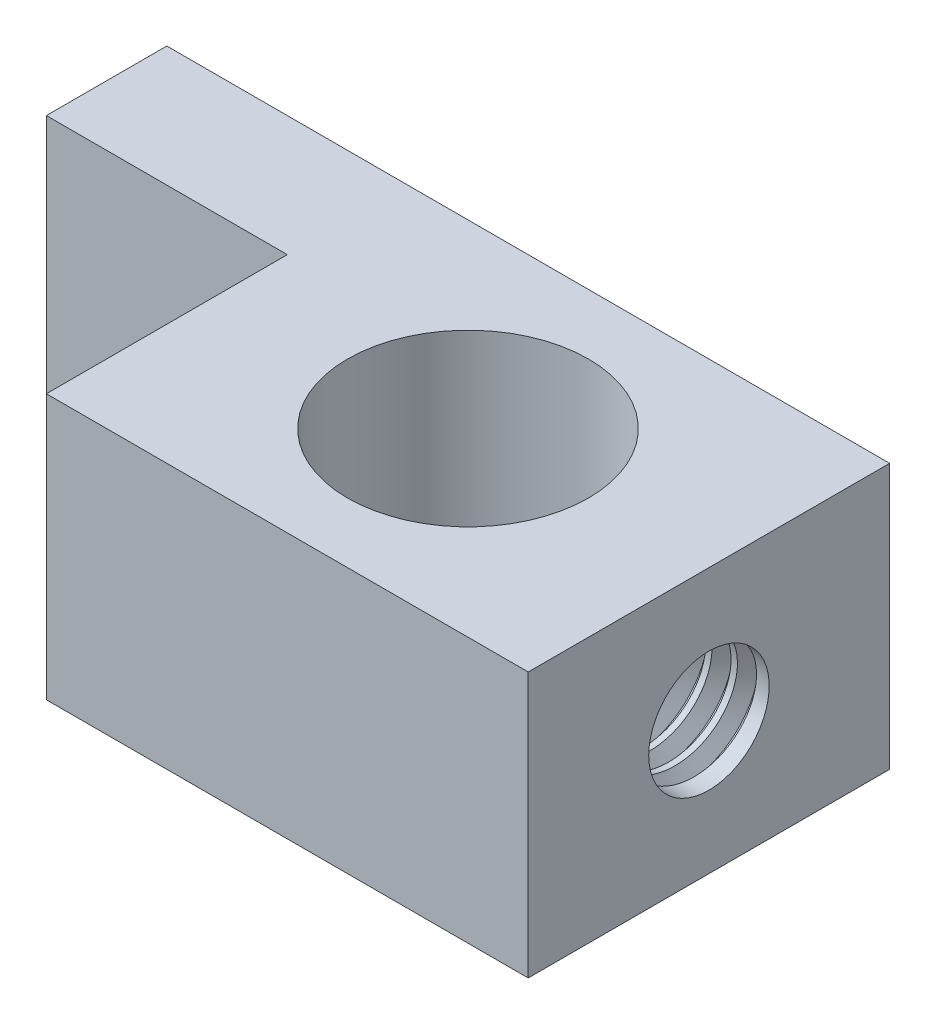
SolidWorks part; units mm, degrees
ref_plane "Front Plane" through (0, 0, 0) normal (0, 0, 1) x (1, 0, 0)
ref_plane "Top Plane" through (0, 0, 0) normal (0, 1, 0) x (1, 0, 0)
ref_plane "Right Plane" through (0, 0, 0) normal (1, 0, 0) x (0, 0, -1)
sketch "Sketch1" plane through (0, 0, 0) normal (0, 0, 1) x (1, 0, 0)
  line L1 (0, 0) -> (-20, 0)
  line L2 (0, 0) -> (0, -11)
  line L3 (0, -11) -> (-20, -11)
  line L4 (-20, 0) -> (-20, -11)
  dimension "D1" = 11
  dimension "D2" = 20
extrude "Boss-Extrude1" add sketch "Sketch1" along normal blind 15
sketch "Sketch3" plane through (0, 0, 0) normal (0, 1, 0) x (1, 0, 0)
  line L0 (0, -15) -> (-20, -15) construction
  line L1 (0, -15) -> (0, 0) construction
  circle A0 centre (-10, -7.5) radius 5
  point P4 (-10, -15)
  point P7 (0, -7.5)
  dimension "D1" = 0
  dimension "D2" = 0
  dimension "D3" = 10
extrude "Cut-Extrude1" cut sketch "Sketch3" against normal blind 26
sketch "Sketch4" plane through (0, 0, 0) normal (1, 0, 0) x (0, 0, -1)
  line L0 (-15, 0) -> (0, 0) construction
  line L1 (0, -11) -> (0, 0) construction
  circle A0 centre (-7.5, -5.5) radius 2.5
  point P4 (-7.5, 0)
  point P7 (0, -5.5)
  dimension "D1" = 0
  dimension "D2" = 0
  dimension "D3" = 5
extrude "Cut-Extrude2" cut sketch "Sketch4" against normal blind 9
sketch "Sketch6" plane through (-20, 0, 0) normal (-1, 0, 0) x (0, 0, 1)
  line L0 (15, 0) -> (0, 0) construction
  line L1 (0, -11) -> (5, -11)
  line L2 (0, -11) -> (0, 0)
  line L3 (0, 0) -> (5, 0)
  line L4 (5, -11) -> (5, 0)
  dimension "D1" = 5
extrude "Boss-Extrude4" add sketch "Sketch6" along normal blind 10
thread "Thread1" pitch 1.0583 method cut profile "Thread Profile1" start angle 0, offset 0, length 6, pitch 1.0583, diameter 5
ref_plane "Plane1" through (0, -5.5, 10) normal (0, -1, 0) x (0, 0, 1)
sketch "Thread Profile1" plane through (0, -5.5, 10) normal (0, -1, 0) x (0, 0, 1)
  line L0 (0, 0) -> (0, 1.0583) construction
  line L1 (0, 0) -> (0.5728, 0.3307)
  line L2 (0.5728, 0.3307) -> (0.5728, 0.463)
  line L3 (0.5728, 0.463) -> (0, 0.7937)
  line L4 (0.5728, 0.3969) -> (0, 0.3969) construction
  line L11 (0, 0) -> (0, 0.7937)
  point P2 (0, 0)
  dimension "Pitch" = 1.0583
  dimension "Profile_Angle" = 60
  dimension "Profile_Land" = 0.1323
  dimension "Profile_Height" = 0.5728
